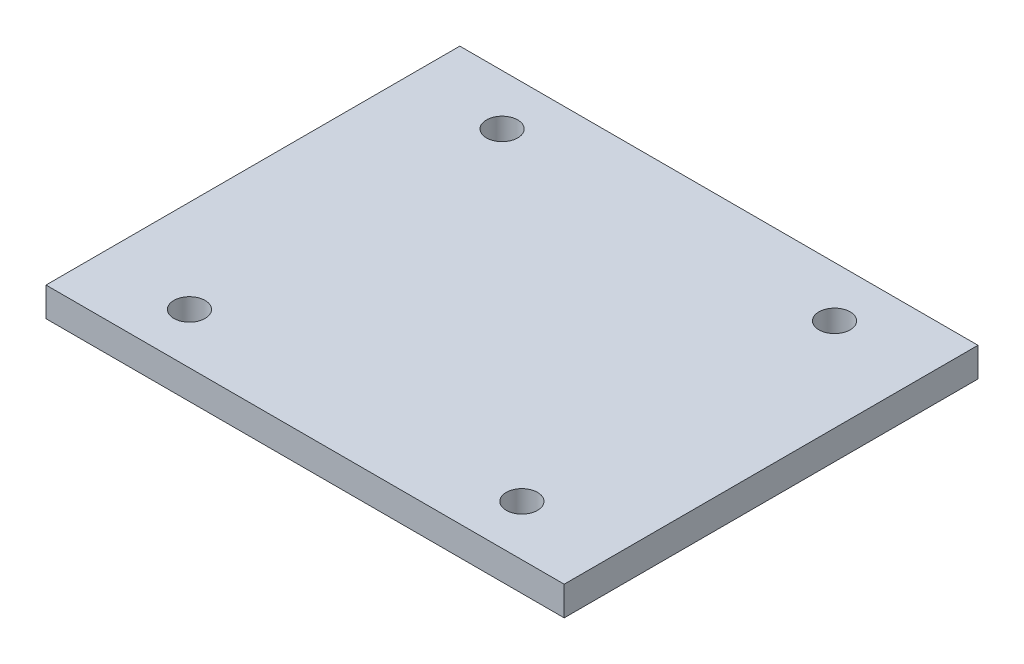
SolidWorks part; units mm, degrees
ref_plane "Front Plane" through (0, 0, 0) normal (0, 0, 1) x (1, 0, 0)
ref_plane "Top Plane" through (0, 0, 0) normal (0, 1, 0) x (1, 0, 0)
ref_plane "Right Plane" through (0, 0, 0) normal (1, 0, 0) x (0, 0, -1)
sketch "Sketch2" plane through (0, 0, 0) normal (0, 1, 0) x (1, 0, 0)
  line L0 (0, 0) -> (0, 90)
  line L1 (0, 90) -> (112.7, 90)
  line L2 (112.7, 90) -> (112.7, 0)
  line L3 (112.7, 0) -> (0, 0)
  dimension "D1" = 112.7
  dimension "D2" = 90
extrude "Boss-Extrude1" add sketch "Sketch2" along normal blind 6.35
sketch "Sketch3" plane through (0, 6.35, 0) normal (0, 1, 0) x (1, 0, 0)
  line L0 (1.35, 90) -> (1.35, 0) construction
  line L1 (112.7, 90) -> (0, 90) construction
  line L2 (0, 0) -> (112.7, 0) construction
  line L3 (111.35, 90) -> (111.35, 0) construction
  line L4 (56.35, 90) -> (56.35, 0) construction
  line L5 (1.35, 45) -> (56.35, 45) construction
  line L6 (56.35, 45) -> (111.35, 45) construction
  circle A0 centre (20.2, 79) radius 3.4
  circle A1 centre (20.2, 11) radius 3.4
  circle A2 centre (92.5, 11) radius 3.4
  circle A3 centre (92.5, 79) radius 3.4
  dimension "D4" = 6.8
  dimension "D1" = 110
  dimension "D2" = 18.85
  dimension "D3" = 11
extrude "Mounting Holes" cut sketch "Sketch3" against normal through all
equation "\"L1L\"=500"
equation "\"L1Thick\"=6.35"
equation "\"Harm-Drive-Outer\"=74.5"
equation "\"L1-Spacing\"=100"
equation "\"L-Bracket-HoleToWall\"=12.5"
equation "\"D2@Sketch3\"=\"L-Bracket-HoleToWall\"+\"L1Thick\""
equation "\"D3@Sketch3\"=\"L-Bracket-HoleToSide\""
equation "\"L-Bracket-HoleToSide\"=11"
equation "\"D1@Sketch3\"=\"L1-Spacing\""
equation "\"Bracket-Hole-D\"=6.8"
equation "\"D4@Sketch3\"=\"Bracket-Hole-D\""
equation "\"L1-Spacing\"=110"
